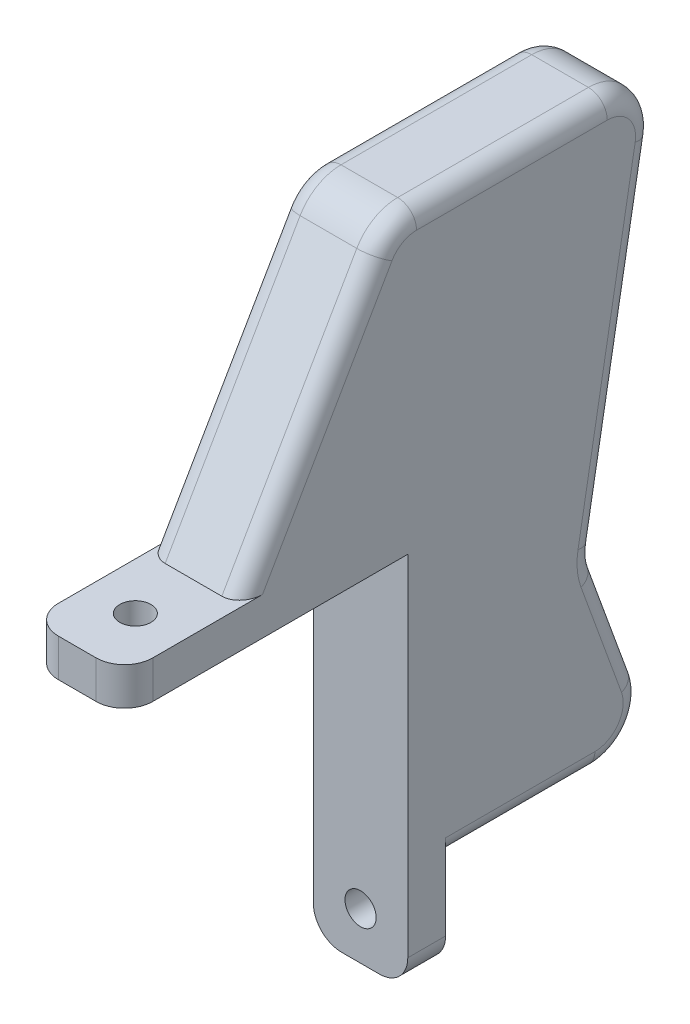
SolidWorks part; units mm, degrees
ref_plane "Front Plane" through (0, 0, 0) normal (0, 0, 1) x (1, 0, 0)
ref_plane "Top Plane" through (0, 0, 0) normal (0, 1, 0) x (1, 0, 0)
ref_plane "Right Plane" through (0, 0, 0) normal (1, 0, 0) x (0, 0, -1)
sketch "Sketch1" plane through (0, 0, 0) normal (1, 0, 0) x (0, 0, -1)
  line L0 (0, 0) -> (20, 0)
  line L1 (0, 0) -> (18.0413, 31.2484)
  line L2 (18.0413, 31.2484) -> (47.0794, 31.2484)
  line L4 (46.9482, -30) -> (20, -30)
  line L6 (20, 0) -> (20, -30)
  line L8 (20, -30) -> (32.0088, -30) construction
  line L9 (47.0794, 31.2484) -> (39.7613, -10.2542)
  line L10 (39.7613, -10.2542) -> (46.9482, -30)
  point P7 (129.2231, -65.6061)
  point P8 (105.9642, -27.8844)
  point P11 (48.1622, -65.9816)
  point P12 (110.8422, -60)
  point P13 (103.5649, -60)
  point P14 (77.8022, -32.6634)
  point P15 (61.4452, 38.5107)
  point P16 (62.6543, -40)
  point P17 (45.9176, -9.5496)
  point P18 (48.2687, -14.5284)
  point P19 (58.2262, -30)
  point P20 (45.7462, -30)
  point P21 (39.5696, -9.7872)
  point P22 (50.3443, -30)
  point P23 (36.3075, -13.0685)
  point P24 (39.7613, -10.2542)
  dimension "D1" = 20
  dimension "D2" = 60
  dimension "D3" = 70
  dimension "D4" = 80
  dimension "D7" = 30
extrude "Boss-Extrude1" add sketch "Sketch1" along normal blind 10
fillet "Fillet1" radius 5 4 edges at (5, -30, -46.9482) (5, -10.2542, -39.7613) (5, 31.2484, -47.0794) (5, 31.2484, -18.0413)
sketch "Sketch2" plane through (0, 0, 0) normal (0, -1, 0) x (1, 0, 0)
  line L0 (0, -20) -> (0, 0)
  line L1 (0, 0) -> (0, 10)
  line L2 (0, 10) -> (10, 10)
  line L3 (10, 10) -> (10, 0)
  line L4 (10, 0) -> (10, -20)
  line L5 (10, -20) -> (0, -20)
  line L6 (10, 0) -> (0, 0) construction
extrude "Boss-Extrude2" add sketch "Sketch2" against normal blind 4
sketch "Sketch3" plane through (0, 4, 0) normal (0, 1, 0) x (1, 0, 0)
  line L0 (5, -10) -> (5, 2.3094) construction
  line L1 (10, -10) -> (0, -10) construction
  line L2 (0, 2.3094) -> (10, 2.3094) construction
  circle A0 centre (5, -3.8453) radius 1.65
  dimension "D1" = 3.3
extrude "Cut-Extrude1" cut sketch "Sketch3" against normal through all
sketch "Sketch4" plane through (0, 0, -20) normal (0, 0, 1) x (1, 0, 0)
  line L0 (0, 0) -> (0, -30)
  line L1 (0, -30) -> (0, -40)
  line L2 (0, -40) -> (10, -40)
  line L3 (10, -40) -> (10, -30)
  line L4 (10, -30) -> (10, 0)
  line L5 (10, 0) -> (0, 0)
  line L6 (10, -30) -> (0, -30) construction
extrude "Boss-Extrude3" add sketch "Sketch4" against normal blind 4
sketch "Sketch5" plane through (0, 0, -24) normal (0, 0, -1) x (-1, 0, 0)
  line L0 (-5, -30) -> (-5, -40) construction
  line L1 (0, -30) -> (-10, -30) construction
  line L2 (0, -40) -> (-10, -40) construction
  circle A0 centre (-5, -35) radius 1.65
  dimension "D1" = 3.3
extrude "Cut-Extrude2" cut sketch "Sketch5" against normal through all
fillet "Fillet2" radius 3 4 edges at (0, -40, -22) (10, -40, -22) (0, 2, 10) (10, 2, 10)
fillet "Fillet3" radius 2 18 edges at (0, -30, -31.9037) (0, -27.8679, -43.9032) (0, -17.4015, -42.3628) (0, -10.2388, -39.9371) (0, 8.2227, -43.0193) (0, 29.4623, -44.9508) (0, 31.2484, -31.0243) (0, 30.5785, -18.428) (10, -30, -31.9037) (10, -27.8679, -43.9032) (10, -17.4015, -42.3628) (10, -10.2388, -39.9371) (10, 8.2227, -43.0193) (10, 29.4623, -44.9508) (10, 31.2484, -31.0243) (10, 30.5785, -18.428) (0, 16.3742, -9.4537) (10, 16.3742, -9.4537)
